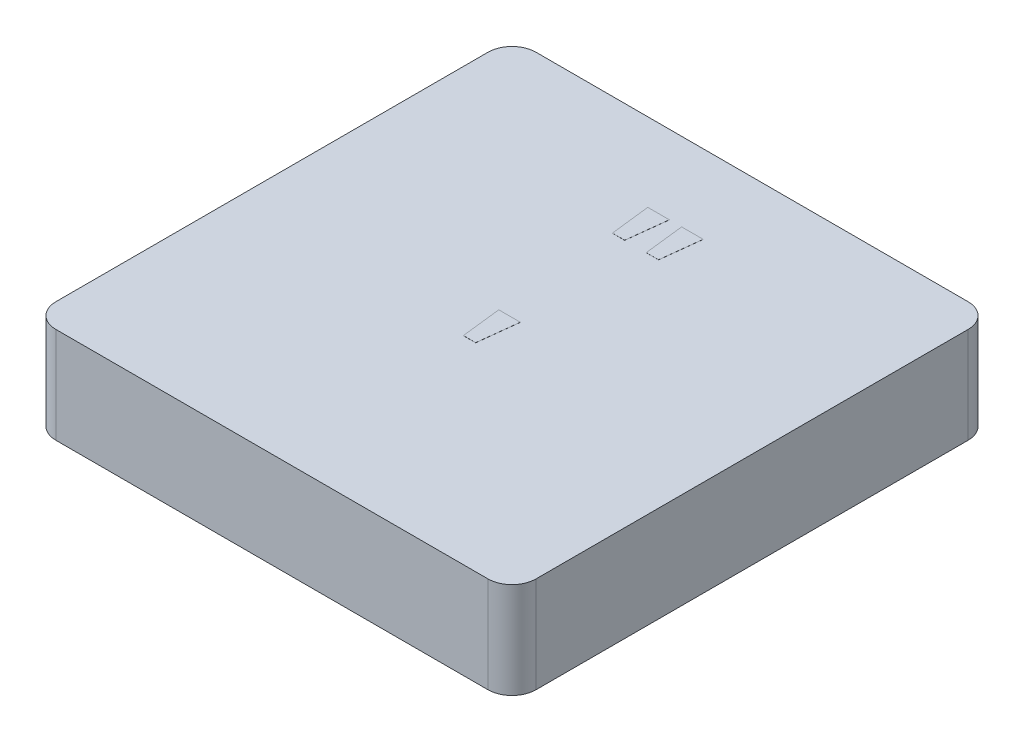
SolidWorks part; units mm, degrees
ref_plane "Front Plane" through (0, 0, 0) normal (0, 0, 1) x (1, 0, 0)
ref_plane "Top Plane" through (0, 0, 0) normal (0, 1, 0) x (1, 0, 0)
ref_plane "Right Plane" through (0, 0, 0) normal (1, 0, 0) x (0, 0, -1)
sketch "Sketch1" plane through (0, 0, 0) normal (0, 1, 0) x (1, 0, 0)
  line L0 (0, 0) -> (12.7, 0)
  line L1 (12.7, 0) -> (12.7, 12.7)
  line L2 (12.7, 12.7) -> (0, 12.7)
  line L3 (0, 12.7) -> (0, 0)
  dimension "D1" = 12.7
  dimension "D2" = 12.7
extrude "Boss-Extrude1" add sketch "Sketch1" along normal blind 2.54
fillet "Fillet1" radius 0.635 4 edges at (0, 1.27, -12.7) (12.7, 1.27, -12.7) (12.7, 1.27, 0) (0, 1.27, 0)
shell "Shell1" thickness 0.635 removed face at (6.35, 0, -6.35)
sketch "Sketch2" plane through (0, 1.905, 0) normal (0, -1, 0) x (-1, 0, 0)
  line L0 (-0.635, 6.35) -> (-12.065, 6.35) construction
  line L1 (-0.635, 12.065) -> (-0.635, 0.635) construction
  line L2 (-12.065, 0.635) -> (-12.065, 12.065) construction
  line L3 (-6.35, 0.635) -> (-6.35, 12.065) construction
  line L4 (-0.635, 0.635) -> (-12.065, 0.635) construction
  line L5 (-12.065, 12.065) -> (-0.635, 12.065) construction
  circle A0 centre (-6.35, 6.35) radius 2.54
  dimension "D1" = 5.08
extrude "Boss-Extrude2" add sketch "Sketch2" along normal up to surface (1.905 mm away) up to face at (6.35, 0, -6.35)
sketch "Sketch3" plane through (0, 2.54, 0) normal (0, 1, 0) x (1, 0, 0)
  line L0 (0.635, 0) -> (12.065, 0) construction
  line L1 (0, 12.065) -> (0, 0.635) construction
  line L2 (12.065, 12.7) -> (0.635, 12.7) construction
  text T0 "<b>\"</b>"
  text T1 "<b>'</b>\r\n"
  dimension "D1" = 3.048
  dimension "D2" = 5.842
  dimension "D3" = 5.334
  dimension "D4" = 5.588
extrude "Boss-Extrude3" add sketch "Sketch3" along normal blind 0.0025
